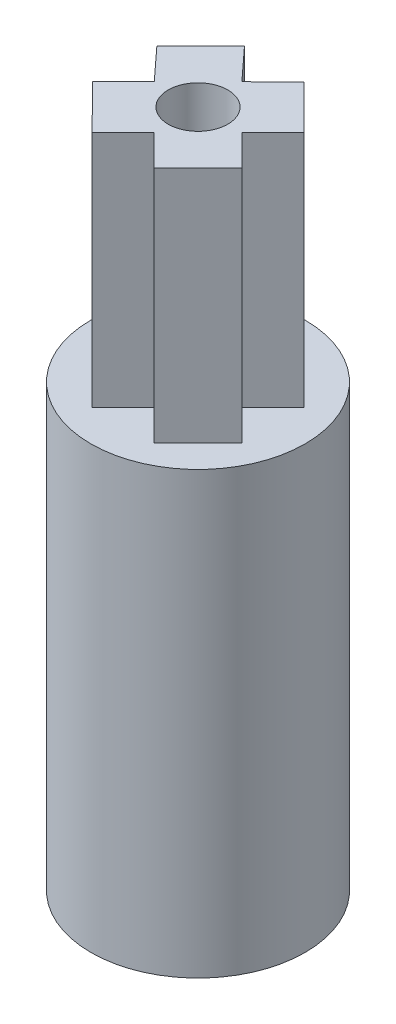
SolidWorks part; units mm, degrees
ref_plane "Front Plane" through (0, 0, 0) normal (0, 0, 1) x (1, 0, 0)
ref_plane "Top Plane" through (0, 0, 0) normal (0, 1, 0) x (1, 0, 0)
ref_plane "Right Plane" through (0, 0, 0) normal (1, 0, 0) x (0, 0, -1)
sketch "Sketch1" plane through (0, 0, 0) normal (0, 1, 0) x (1, 0, 0)
  circle A2 centre (0, 0) radius 5.715
  dimension "D3" = 11.43
extrude "Boss-Extrude1" add sketch "Sketch1" along normal blind 23.495
sketch "Sketch5" plane through (0, 23.495, 0) normal (0, 1, 0) x (1, 0, 0)
  line L0 (0, 2.5411) -> (-1.7512, 4.3809) construction
  line L1 (-2.54, -2.54) -> (2.54, -2.54) construction
  line L2 (-2.54, -2.54) -> (-2.54, 2.54) construction
  line L3 (-2.54, 2.54) -> (2.54, 2.54) construction
  line L4 (2.54, -2.54) -> (2.54, 2.54) construction
  line L5 (-2.54, -2.54) -> (2.54, 2.54) construction
  line L6 (-2.54, 2.54) -> (2.54, -2.54) construction
  line L7 (-2.54, 0.0011) -> (-4.2912, 1.8409) construction
  line L8 (-4.2912, 1.8409) -> (-1.7512, 4.3809) construction
  line L9 (2.54, 0) -> (4.3361, -1.7961) construction
  line L10 (0, -2.54) -> (1.7961, -4.3361) construction
  line L11 (1.7961, -4.3361) -> (4.3361, -1.7961) construction
  line L12 (-2.54, 0.0011) -> (-4.3359, -1.7951) construction
  line L13 (0, -2.54) -> (-1.7964, -4.3357) construction
  line L14 (-4.3359, -1.7951) -> (-1.7964, -4.3357) construction
  line L15 (2.54, 0) -> (4.3364, 1.7957) construction
  line L16 (1.797, 4.3362) -> (4.3364, 1.7957) construction
  line L17 (0, 2.5411) -> (1.797, 4.3362) construction
  line L18 (0, 2.3397) -> (1.6556, 3.9889)
  line L19 (-3.9887, -1.6499) -> (-1.6534, -3.9881)
  line L20 (-3.9181, 1.7234) -> (-1.5813, 4.0602)
  line L21 (0, -2.3368) -> (1.6524, -3.9892)
  line L22 (1.6524, -3.9892) -> (3.9892, -1.6524)
  line L23 (-2.3368, 0.0029) -> (-3.9887, -1.6499)
  line L24 (0, -2.3368) -> (-1.6534, -3.9881)
  line L25 (2.3368, 0) -> (3.9909, 1.6506)
  line L26 (0, 2.3397) -> (-1.5813, 4.0602)
  line L27 (-2.3368, 0.0029) -> (-3.9181, 1.7234)
  line L28 (1.6556, 3.9889) -> (3.9909, 1.6506)
  line L29 (2.3368, 0) -> (3.9892, -1.6524)
  point P0 (0, 0)
  dimension "D1" = 2.54
  dimension "D2" = 5.08
  dimension "D3" = 5.08
  dimension "D4" = 8.6721
  dimension "D5" = 3.5921
  dimension "D6" = 3.5921
  dimension "D7" = 3.5921
  dimension "D8" = 3.5921
  dimension "D9" = 8.6721
  dimension "D10" = 0
  dimension "D11" = 3.5921
  dimension "D12" = 5.08
  dimension "D13" = 2.54
  dimension "D14" = 2.54
  dimension "D15" = 2.54
  dimension "D16" = 2.54
  dimension "D17" = 2.54
  dimension "D18" = 2.54
  dimension "D19" = 2.54
  dimension "D20" = 2.54
extrude "Boss-Extrude3" add sketch "Sketch5" along normal blind 12.7
sketch "Sketch6" plane through (0, 36.195, 0) normal (0, 1, 0) x (1, 0, 0)
  circle A0 centre (0, 0) radius 1.5875
  dimension "D1" = 3.175
extrude "Cut-Extrude1" cut sketch "Sketch6" against normal up to surface (12.7 mm away) up to face at (0.0122, 23.495, -0.0125)
